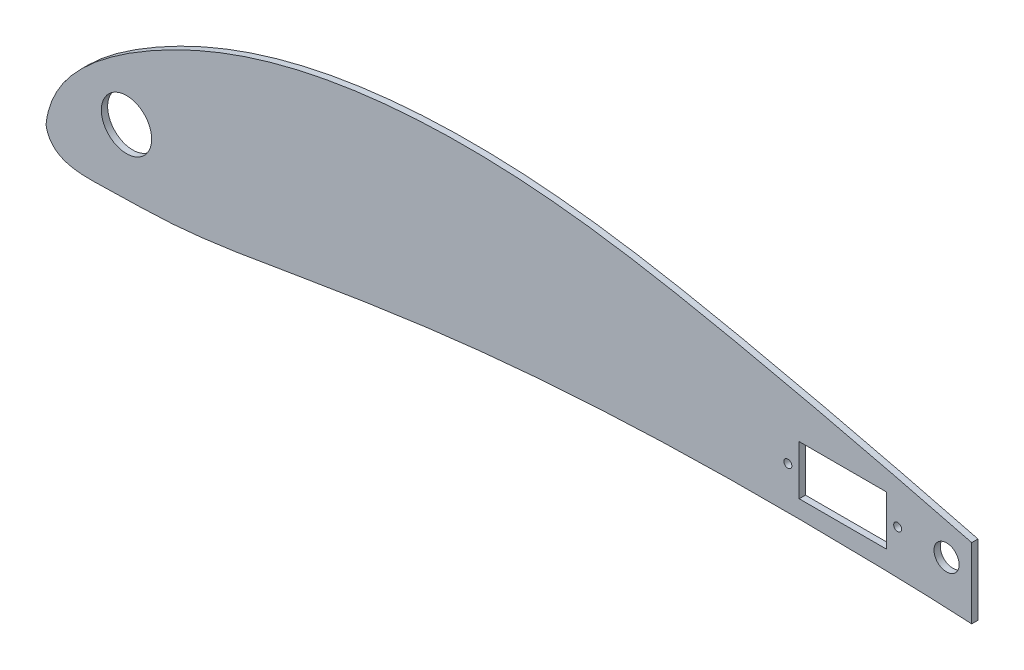
SolidWorks part; units mm, degrees
ref_plane "Front Plane" through (0, 0, 0) normal (0, 0, 1) x (1, 0, 0)
ref_plane "Top Plane" through (0, 0, 0) normal (0, 1, 0) x (1, 0, 0)
ref_plane "Right Plane" through (0, 0, 0) normal (1, 0, 0) x (0, 0, -1)
sketch "Sketch1" plane through (0, 0, 0) normal (0, 0, 1) x (1, 0, 0)
  spline S0 degree 3 poles (0.0006, 0.0001) (0.8106, 7.3592) (8.6491, 17.8566) (26.2867, 29.9752) (52.1111, 42.0692) (89.5976, 49.2908) (131.4008, 47.8848) (173.2567, 40.0411) (217.9611, 29.613) (256.9521, 19.5289) (290.3598, 8.711) (301.2732, 4.3828) (314.8169, -0.5162) (309.8463, 0.0001) knots 0 0 0 0 0.060864 0.113688 0.188609 0.312909 0.448482 0.557612 0.691544 0.852438 0.929756 0.976058 1 1 1 1
  spline S1 degree 3 poles (309.8463, 0.0001) (303.9568, 1.471) (293.9895, 2.094) (276.264, 4.5144) (260.8463, 5.4274) (235.8588, 7.8703) (205.1014, 8.8381) (157.7186, 9.0307) (110.4973, 6.1815) (66.5062, -0.5867) (36.4547, -6.0985) (15.3166, -6.1891) (1.2307, -6.9241) (0.0006, 0.0001) knots 0 0 0 0 0.057787 0.095275 0.171021 0.205339 0.335319 0.464904 0.658702 0.785512 0.893517 0.943092 1 1 1 1
extrude "Boss-Extrude1" add sketch "Sketch1" along normal blind 1.5875
sketch "Sketch2" plane through (0, 0, 1.5875) normal (0, 0, 1) x (1, 0, 0)
  circle A0 centre (20.32, 10.16) radius 6.35
  circle A1 centre (227.2963, 19.0501) radius 3.175
  dimension "D2" = 12.7
  dimension "D3" = 6.35
  dimension "D6" = 20.32
  dimension "D1" = 82.55
  dimension "D4" = 19.05
  dimension "D5" = 10.16
extrude "Cut-Extrude1" cut sketch "Sketch2" against normal through all
sketch "Sketch3" plane through (0, 0, 1.5875) normal (0, 0, 1) x (1, 0, 0)
  line L1 (350.4863, -6.3499) -> (233.6463, -6.3499)
  line L2 (350.4863, -6.3499) -> (350.4863, 44.4501)
  line L3 (350.4863, 44.4501) -> (233.6463, 44.4501)
  line L4 (233.6463, -6.3499) -> (233.6463, 44.4501)
  circle A0 centre (227.2963, 19.0501) radius 3.175 construction
  dimension "D1" = 6.35
  dimension "D2" = 116.84
  dimension "D3" = 50.8
  dimension "D4" = 44.45
extrude "Cut-Extrude2" cut sketch "Sketch3" against normal through all contours L3 L4 L1 L2
sketch "Sketch4" plane through (0, 0, 1.5875) normal (0, 0, 1) x (1, 0, 0)
  line L0 (190.0992, 19.5181) -> (187.2492, 19.5181) construction
  line L1 (190.0992, 25.7681) -> (212.0992, 25.7681)
  line L2 (190.0992, 25.7681) -> (190.0992, 13.2681)
  line L3 (190.0992, 13.2681) -> (212.0992, 13.2681)
  line L4 (212.0992, 25.7681) -> (212.0992, 13.2681)
  line L5 (212.0992, 19.5181) -> (214.9492, 19.5181) construction
  circle A0 centre (214.9492, 19.5181) radius 1.0008
  circle A1 centre (187.2492, 19.5181) radius 1.0008
  dimension "D4" = 2.0015
  dimension "D1" = 2.85
  dimension "D2" = 22
  dimension "D3" = 12.5
extrude "Cut-Extrude3" cut sketch "Sketch4" against normal through all
